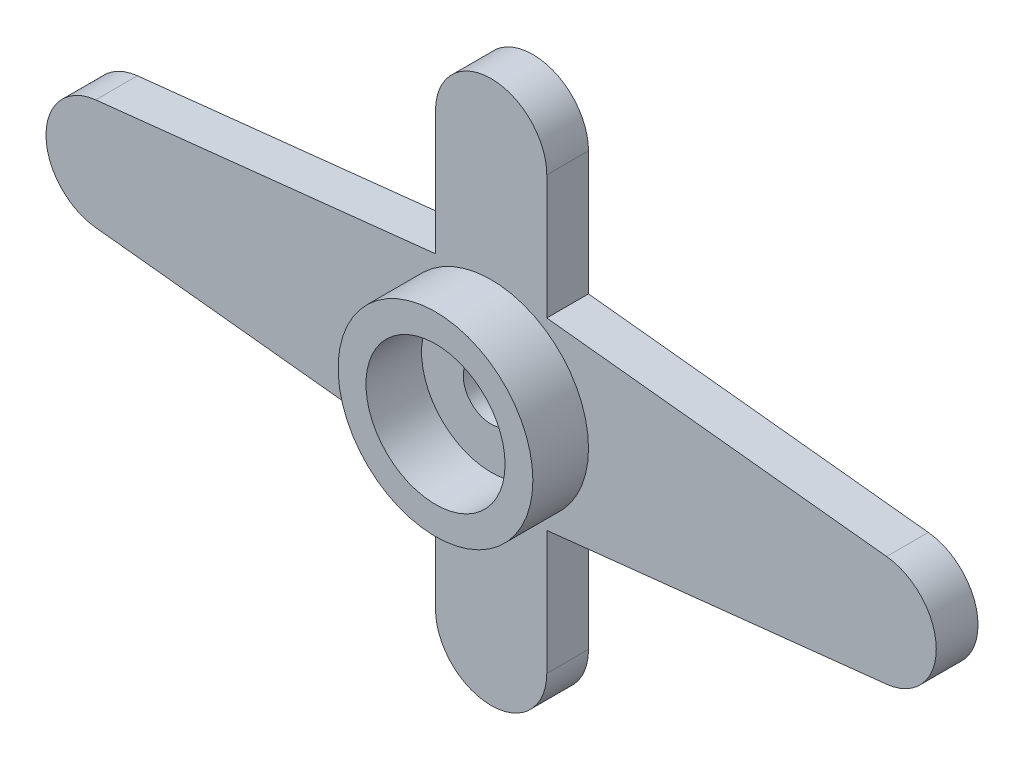
SolidWorks part; units mm, degrees
ref_plane "Front Plane" through (0, 0, 0) normal (0, 0, 1) x (1, 0, 0)
ref_plane "Top Plane" through (0, 0, 0) normal (0, 1, 0) x (1, 0, 0)
ref_plane "Right Plane" through (0, 0, 0) normal (1, 0, 0) x (0, 0, -1)
sketch "Sketch1" plane through (0, 0, 0) normal (0, 0, 1) x (1, 0, 0)
  line L0 (0, 0) -> (0, 10.3254) construction
  line L1 (0, 0) -> (16, 0) construction
  line L2 (2, 7.7586) -> (2, 3.3047)
  line L3 (2, 3.3047) -> (14.2143, 1.9885)
  line L4 (2, -3.3047) -> (14.2143, -1.9885)
  line L5 (2, -7.7586) -> (2, -3.3047)
  line L6 (-2, -7.7586) -> (-2, -3.3047)
  line L7 (-2, -3.3047) -> (-14.2143, -1.9885)
  line L8 (-2, 3.3047) -> (-14.2143, 1.9885)
  line L9 (-2, 7.7586) -> (-2, 3.3047)
  arc A0 (3.5, 0) -> (0, 3.5) centre (0, 0) ccw construction
  arc A1 (2.5, 0) -> (0, 2.5) centre (0, 0) ccw construction
  arc A2 (14.2143, -1.9885) -> (14.2143, 1.9885) centre (14, 0) ccw
  arc A3 (2, 7.7586) -> (-2, 7.7586) centre (0, 7.7586) ccw
  arc A4 (2, -7.7586) -> (-2, -7.7586) centre (0, -7.7586) cw
  arc A5 (-14.2143, -1.9885) -> (-14.2143, 1.9885) centre (-14, 0) cw
  dimension "D1" = 7
  dimension "D2" = 5
  dimension "D3" = 4
  dimension "D4" = 4
extrude "Boss-Extrude1" add sketch "Sketch1" along normal blind 1.5
sketch "Sketch2" plane through (0, 0, 1.5) normal (0, 0, 1) x (1, 0, 0)
  circle A0 centre (0, 0) radius 3.5
  circle A1 centre (0, 0) radius 2.5
  dimension "D1" = 7
  dimension "D2" = 5
extrude "Boss-Extrude2" add sketch "Sketch2" along normal blind 2.2
sketch "Sketch3" plane through (0, 0, 1.5) normal (0, 0, 1) x (1, 0, 0)
  circle A0 centre (0, 0) radius 1
  dimension "D1" = 2
extrude "Cut-Extrude1" cut sketch "Sketch3" against normal up to next
sketch "Sketch4" plane through (0, 0, 0) normal (0, 0, -1) x (-1, 0, 0)
  circle A0 centre (0, 0) radius 2.5
  dimension "D1" = 5
extrude "Cut-Extrude2" cut sketch "Sketch4" against normal blind 1
sketch "Çizim1" plane through (0, 0, 0) normal (0, 1, 0) x (1, 0, 0)
  line L0 (-3.5, -3.7) -> (3.5, -3.7) construction
  line L1 (4.5132, -3.5) -> (-4.7716, -3.5)
  line L2 (4.5132, -3.5) -> (4.5132, -5.5965)
  line L3 (4.5132, -5.5965) -> (-4.7716, -5.5965)
  line L4 (-4.7716, -3.5) -> (-4.7716, -5.5965)
  dimension "D1" = 0.2
extrude "Kes-Ekstrüzyon1" cut sketch "Çizim1" against normal blind 10 and the other way blind 10
